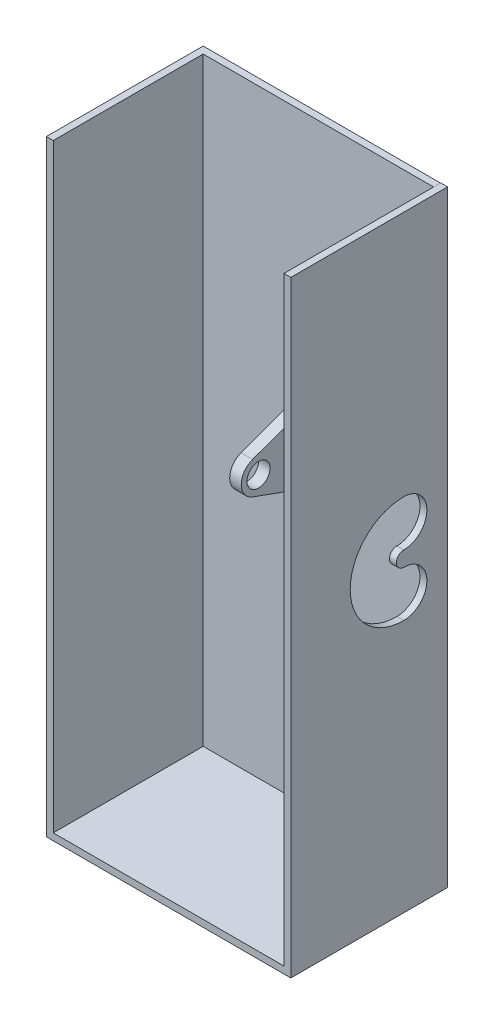
SolidWorks part; units mm, degrees
ref_plane "Front Plane" through (0, 0, 0) normal (0, 0, 1) x (1, 0, 0)
ref_plane "Top Plane" through (0, 0, 0) normal (0, 1, 0) x (1, 0, 0)
ref_plane "Right Plane" through (0, 0, 0) normal (1, 0, 0) x (0, 0, -1)
sketch "Sketch1" plane through (0, 0, 0) normal (0, 0, 1) x (1, 0, 0)
  line L0 (0, 263) -> (0, 0)
  line L1 (0, 0) -> (106, 0)
  line L3 (3, 3) -> (103, 3)
  line L7 (0, 263) -> (3, 263)
  line L8 (3, 3) -> (3, 263)
  line L11 (103, 3) -> (103, 263.0928)
  line L12 (103, 263.0928) -> (106, 263.0928)
  line L13 (106, 0) -> (106, 263.0928)
  point P11 (103.7402, 0)
  point P12 (0, 0)
  dimension "D1" = 3
  dimension "D2" = 3
  dimension "D3" = 260
  dimension "D4" = 100
  dimension "D5" = 3
extrude "Boss-Extrude1" add sketch "Sketch1" along normal blind 68
sketch "Sketch2" plane through (0, 0, 0) normal (0, 0, 1) x (1, 0, 0)
  line L1 (0, 263) -> (106, 263)
  line L2 (0, 263) -> (0, 0)
  line L3 (0, 0) -> (106, 0)
  line L4 (106, 263) -> (106, 0)
  point P4 (-67.5563, 200.5563)
  point P6 (0, 0)
  point P7 (0, 0)
  point P11 (0, 263)
  point P13 (0, 0)
  point P14 (0, 0)
  point P15 (106, 0)
extrude "Boss-Extrude2" add sketch "Sketch2" along normal blind 3
ref_plane "Plane1" through (43, 0, 0) normal (1, 0, 0) x (0, 0, -1)
sketch "Sketch3" plane through (43, 0, 0) normal (1, 0, 0) x (0, 0, -1)
  line L2 (-21.5652, 140.0477) -> (-3, 146.8049)
  line L3 (-3, 3) -> (-3, 263) construction
  line L4 (-3, 146.8049) -> (-3, 119.1951)
  line L5 (-3, 119.1951) -> (-21.5652, 125.9523)
  line L7 (-68, 3) -> (-3, 3) construction
  arc A0 (-21.5652, 140.0477) -> (-21.5652, 125.9523) centre (-19, 133) ccw
  circle A1 centre (-19, 133) radius 5
  point P1 (0, 0)
  point P4 (0, 0)
  point P5 (0, 0)
  dimension "D2" = 15
  dimension "D5" = 10
  dimension "D1" = 16
  dimension "D3" = 130
  dimension "D4" = 70
extrude "Boss-Extrude3" add sketch "Sketch3" against normal blind 5
ref_plane "Plane2" through (63, 0, 0) normal (1, 0, 0) x (0, 0, -1)
sketch "Sketch6" plane through (63, 0, 0) normal (1, 0, 0) x (0, 0, -1)
  line L0 (-19, 138) -> (-3, 138)
  line L2 (-3, 138) -> (-3, 128)
  line L3 (-3, 128) -> (-19, 128)
  line L4 (-3, 263) -> (-3, 3) construction
  arc A0 (-19, 138) -> (-19, 128) centre (-19, 133) ccw
  circle A1 centre (-19, 133) radius 5 construction
  point P1 (0, 0)
  point P7 (-4.177, 138)
  point P11 (0, 0)
extrude "Boss-Extrude6" add sketch "Sketch6" along normal blind 8
hole_wizard "M6 Tapped Hole1" positions "Sketch7" profile "Sketch8" tap size "M6" standard "ISO" end condition up to next
sketch "Sketch7" plane through (63, 0, 0) normal (-1, 0, 0) x (0, 0, 1)
  arc A0 (19, 128) -> (19, 138) centre (19, 133) ccw construction
  point P0 (19, 133)
  point P6 (0, 0)
sketch "Sketch8" plane through (63, 133, 19) normal (0, 1, 0) x (0, 0, 1)
  line L0 (0, 0) -> (0, 8)
  line L1 (0, 8) -> (2.5, 8)
  line L2 (2.5, 8) -> (2.5, 0)
  line L5 (2.5, 0) -> (0, 0)
  line L11 (0, -6.35) -> (0, 107.95) construction
  dimension "Thread Major Dia." = 5
  dimension "Thru Tap Drill Depth" = 8
sketch "Sketch10" plane through (103, 0, 0) normal (-1, 0, 0) x (0, 0, 1)
  line L2 (3, 263) -> (3, 3) construction
  line L4 (19, 146.25) -> (19, 119.75) construction
  arc A0 (19, 146.25) -> (19, 119.75) centre (19, 133) cw construction
  arc A1 (19, 109.75) -> (19, 156.25) centre (19, 133) ccw
  arc A2 (19, 129.75) -> (19, 136.25) centre (19, 133) ccw
  arc A3 (19, 129.75) -> (19, 109.75) centre (19, 119.75) ccw
  arc A4 (19, 156.25) -> (19, 136.25) centre (19, 146.25) ccw
  point P5 (32.25, 133)
  point P13 (17.9997, 118.8673)
  point P14 (0, 0)
  point P15 (19, 134.1317)
  point P16 (19, 135.5044)
  point P17 (19, 123.3332)
  point P20 (3, 133)
  dimension "D3" = 10
  dimension "D1" = 16
  dimension "D2" = 13.25
extrude "Cut-Extrude1" cut sketch "Sketch10" against normal up to next
